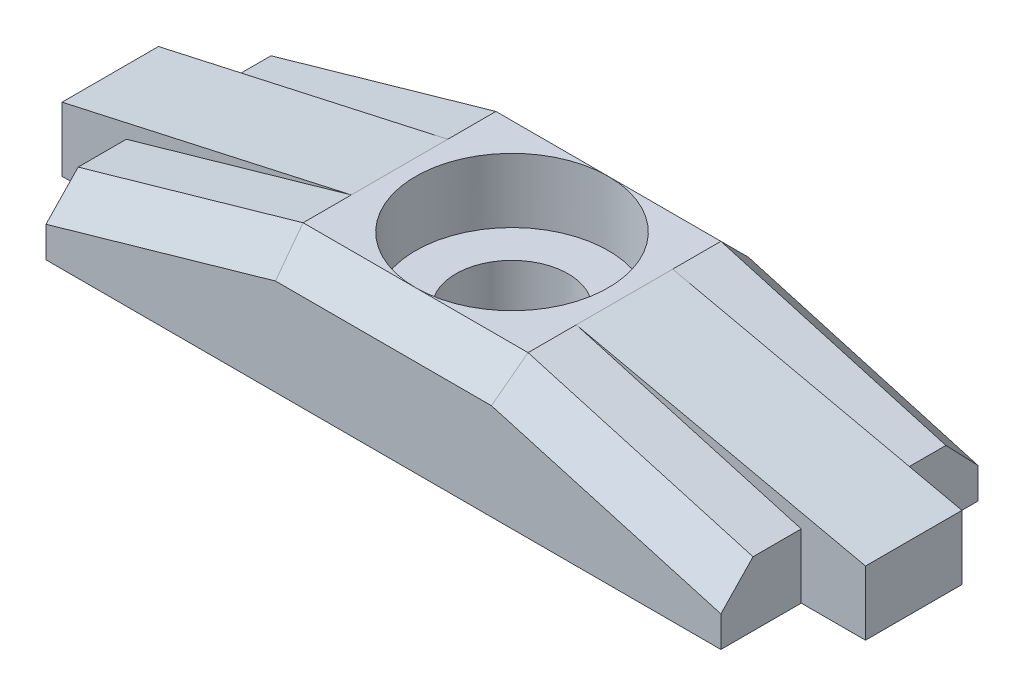
SolidWorks part; units mm, degrees
material "ABS"
ref_plane "Front Plane" through (0, 0, 0) normal (0, 0, 1) x (1, 0, 0)
ref_plane "Top Plane" through (0, 0, 0) normal (0, 1, 0) x (1, 0, 0)
ref_plane "Right Plane" through (0, 0, 0) normal (1, 0, 0) x (0, 0, -1)
sketch "Sketch1" plane through (0, 0, 0) normal (0, 1, 0) x (1, 0, 0)
  line L1 (-12.5, -1.5) -> (12.5, -1.5)
  line L2 (-12.5, -1.5) -> (-12.5, 1.5)
  line L3 (-12.5, 1.5) -> (12.5, 1.5)
  line L4 (12.5, -1.5) -> (12.5, 1.5)
  line L5 (-12.5, -1.5) -> (12.5, 1.5) construction
  line L6 (-12.5, 1.5) -> (12.5, -1.5) construction
  line L7 (-10.5, -4) -> (10.5, -4)
  line L8 (-10.5, -4) -> (-10.5, 4)
  line L9 (-10.5, 4) -> (10.5, 4)
  line L10 (10.5, -4) -> (10.5, 4)
  line L11 (-10.5, -4) -> (10.5, 4) construction
  line L12 (-10.5, 4) -> (10.5, -4) construction
  point P0 (0, 0)
  point P6 (0, 0)
  dimension "D1" = 25
  dimension "D2" = 21
  dimension "D3" = 8
  dimension "D4" = 3
extrude "Boss-Extrude1" add sketch "Sketch1" along normal blind 2 contours L7 L10 L1 L8 | L1 L10 L3 L8 | L1 L8 L3 L2 | L10 L1 L4 L3 | L3 L10 L9 L8 region at (-11.5, 0, 0) region at (0, 0, 0) region at (0, 0, 2.75) region at (11.5, 0, 0) region at (0, 0, -2.75)
sketch "Sketch3" plane through (0, 0, 0) normal (0, 0, 1) x (1, 0, 0)
  line L0 (-12.5, 2) -> (-3.5, 4)
  line L1 (-3.5, 4) -> (3.5, 4)
  line L2 (3.5, 4) -> (12.5, 2)
  line L3 (12.5, 2) -> (-12.5, 2)
  point P6 (0, 4)
  dimension "D1" = 7
  dimension "D2" = 2
extrude "Boss-Extrude2" add sketch "Sketch3" along normal up to surface and the other way up to surface up to face at (-11.5, 1, 1.5) other way up to face at (-11.5, 1, -1.5)
sketch "Sketch4" plane through (0, 0, 4) normal (0, 0, 1) x (1, 0, 0)
  line L0 (10.5, 2) -> (3.5, 4)
  line L1 (3.5, 4) -> (12.5, 2) construction
  line L2 (3.5, 4) -> (-3.5, 4)
  line L3 (-3.5, 4) -> (-10.5, 2)
  line L4 (-10.5, 2) -> (10.5, 2)
extrude "Boss-Extrude3" add sketch "Sketch4" against normal up to surface (8 mm away) up to face at (0, 1, -4)
sketch "Sketch5" plane through (0, 4, 0) normal (0, 1, 0) x (1, 0, 0)
  circle A0 centre (0, 0) radius 1.75
  dimension "D1" = 3.5
extrude "Cut-Extrude1" cut sketch "Sketch5" against normal through all
sketch "Sketch6" plane through (0, 4, 0) normal (0, 1, 0) x (1, 0, 0)
  circle A0 centre (0, 0) radius 3
  dimension "D1" = 6
extrude "Cut-Extrude2" cut sketch "Sketch6" against normal offset from surface (2 mm away) 2 up to face at (0, 0, 1.75)
chamfer "Chamfer1" distance 1 angle 45 6 edges at (7, 3, 4) (0, 4, 4) (-7, 3, 4) (-7, 3, -4) (0, 4, -4) (7, 3, -4)
